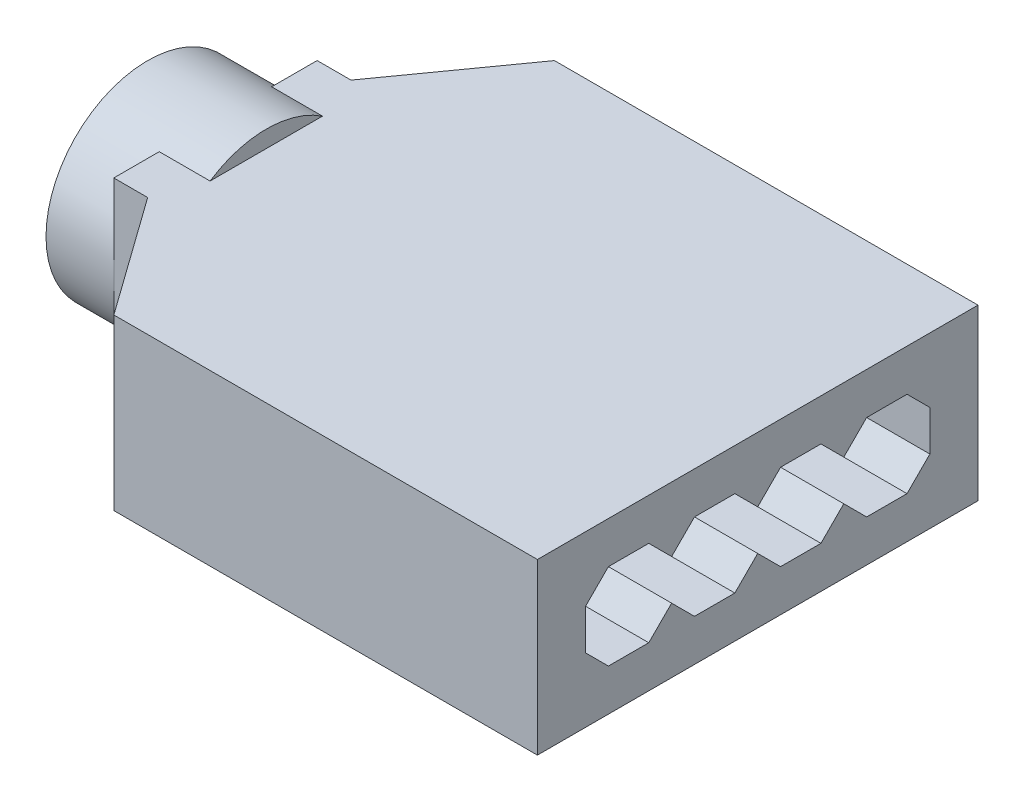
SolidWorks part; units mm, degrees
ref_plane "Alzado" through (0, 0, 0) normal (0, 0, 1) x (1, 0, 0)
ref_plane "Planta" through (0, 0, 0) normal (0, 1, 0) x (1, 0, 0)
ref_plane "Vista lateral" through (0, 0, 0) normal (1, 0, 0) x (0, 0, -1)
sketch "Croquis1" plane through (0, 0, 0) normal (1, 0, 0) x (0, 0, -1)
  line L0 (-0.5955, 1.27) -> (-1.27, 0.5955)
  line L1 (0.5955, 1.27) -> (-0.5955, 1.27)
  line L2 (1.27, 0.5955) -> (1.27, -0.5955)
  line L3 (0.5955, -1.27) -> (-0.5955, -1.27)
  line L4 (-1.27, 0.5955) -> (-1.27, -0.5955)
  line L5 (1.27, 1.27) -> (-1.27, -1.27) construction
  line L6 (1.27, -1.27) -> (-1.27, 1.27) construction
  line L7 (-0.5955, -1.27) -> (-1.27, -0.5955)
  line L8 (1.27, -0.5955) -> (0.5955, -1.27)
  line L9 (1.27, 0.5955) -> (0.5955, 1.27)
  line L10 (0, 0) -> (2.54, 0) construction
  line L11 (2.54, 0) -> (2.54, 3.1915) construction
  line L12 (0, 0) -> (0, 2.4434) construction
  line L13 (1.27, 0.5955) -> (1.27, 2.4434) construction
  line L14 (1.27, -0.5955) -> (1.9445, -1.27)
  line L15 (1.27, 0.5955) -> (1.9445, 1.27)
  line L16 (3.1355, -1.27) -> (3.81, -0.5955)
  line L17 (3.81, 0.5955) -> (3.81, -0.5955)
  line L18 (1.9445, -1.27) -> (3.1355, -1.27)
  line L19 (1.9445, 1.27) -> (3.1355, 1.27)
  line L20 (3.1355, 1.27) -> (3.81, 0.5955)
  line L21 (2.22, -0.32) -> (2.86, 0.32) construction
  line L22 (0.32, 0.32) -> (-0.32, 0.32)
  line L23 (0.32, 0.32) -> (0.32, -0.32)
  line L24 (0.32, -0.32) -> (-0.32, -0.32)
  line L25 (-0.32, 0.32) -> (-0.32, -0.32)
  line L26 (0.32, 0.32) -> (-0.32, -0.32) construction
  line L27 (0.32, -0.32) -> (-0.32, 0.32) construction
  line L28 (2.22, 0.32) -> (2.86, -0.32) construction
  line L29 (2.86, 0.32) -> (2.86, -0.32)
  line L30 (2.22, -0.32) -> (2.86, -0.32)
  line L31 (2.22, 0.32) -> (2.22, -0.32)
  line L32 (2.22, 0.32) -> (2.86, 0.32)
  line L34 (-6.77, 1.5) -> (4.23, 1.5)
  line L35 (-6.77, 1.5) -> (-6.77, -1.5)
  line L36 (-6.77, -1.5) -> (4.23, -1.5)
  line L37 (4.23, 1.5) -> (4.23, -1.5)
  line L38 (-6.77, 1.5) -> (4.23, -1.5) construction
  line L39 (-6.77, -1.5) -> (4.23, 1.5) construction
  point P0 (0, 0)
  point P33 (-1.27, 0)
  point P38 (0, 0)
  dimension "D1" = 2.54
  dimension "D2" = 2.54
  dimension "D3" = 2.54
  dimension "D4" = 0.64
  dimension "D5" = 0.64
  dimension "D6" = 3
  dimension "D7" = 11
extrude "Saliente-Extruir1" add sketch "Croquis1" along normal blind 2.54 contours L2 L9 L1 L0 L4 L7 L3 L8 L25 L22 L23 L24 | L20 L19 L15 L2 L14 L18 L16 L17 L31 L32 L29 L30 region at (0, 1.2341, 0) region at (0, 0.9073, -1.6327)
sketch "Croquis3" plane through (0, 0, 0) normal (1, 0, 0) x (0, 0, -1)
  line L1 (-0.32, -0.32) -> (0.32, -0.32)
  line L2 (-0.32, -0.32) -> (-0.32, 0.32)
  line L3 (-0.32, 0.32) -> (0.32, 0.32)
  line L4 (0.32, -0.32) -> (0.32, 0.32)
  line L5 (2.22, -0.32) -> (2.86, -0.32)
  line L6 (2.22, -0.32) -> (2.22, 0.32)
  line L7 (2.22, 0.32) -> (2.86, 0.32)
  line L8 (2.86, -0.32) -> (2.86, 0.32)
extrude "Saliente-Extruir2" add sketch "Croquis3" along normal blind 8.54 and the other way blind 3 separate body
chamfer "Chaflán1" distance 0.2 angle 45 8 edges at (-3, -0.32, 0) (-3, 0, -0.32) (-3, 0.32, 0) (-3, 0, 0.32) (8.54, 0.32, 0) (8.54, 0, -0.32) (8.54, -0.32, 0) (8.54, 0, 0.32)
chamfer "Chaflán2" distance 0.2 angle 45 8 edges at (8.54, 0.32, -2.54) (8.54, 0, -2.86) (8.54, -0.32, -2.54) (8.54, 0, -2.22) (-3, -0.32, -2.54) (-3, 0, -2.86) (-3, 0.32, -2.54) (-3, 0, -2.22)
mirror "Mirror3" about plane through (2.54, 0, 1.27) normal (0, 0, -1) of bodies 104 103
mirror "Mirror5" about plane through (2.54, 0, 1.27) normal (0, 0, -1) of bodies 101 102
extrude "Boss-Extrude6" add sketch "Croquis1<4>" along normal up to surface (2.54 mm away) separate body contours L37 L34 L35 L36 L19 L20 L17 L16 L18 L14 L8 L3 L7 L4 L0 L1 L9 L15 region at (0, 0, 2.5545) up to face at (2.54, 0, 0)
sketch "Croquis1<4>" plane through (0, 0, 0) normal (1, 0, 0) x (0, 0, -1) same geometry as "Croquis1"
combine bodies "Combine5" operation type subtract main body 121 bodies to subtract 104 103 107 108 110
sketch "Sketch6" plane through (0, 0, 0) normal (-1, 0, 0) x (0, 0, 1)
  line L1 (-4.23, 1.5) -> (6.77, 1.5)
  line L2 (-4.23, 1.5) -> (-4.23, -1.5)
  line L3 (-4.23, -1.5) -> (6.77, -1.5)
  line L4 (6.77, 1.5) -> (6.77, -1.5)
  circle A0 centre (-2.54, 0) radius 1
  circle A1 centre (0, 0.0136) radius 1
  circle A2 centre (2.54, 0) radius 1
  circle A3 centre (5.08, 0) radius 1
extrude "Boss-Extrude11" add sketch "Sketch6" along normal blind 0.8
sketch "Sketch7" plane through (2.54, 0, 0) normal (1, 0, 0) x (0, 0, -1)
  line L1 (-6.77, 1.5) -> (4.23, 1.5)
  line L2 (-6.77, 1.5) -> (-6.77, -1.5)
  line L3 (-6.77, -1.5) -> (4.23, -1.5)
  line L4 (4.23, 1.5) -> (4.23, -1.5)
  line L6 (-6.77, 1.5) -> (4.23, -1.5) construction
  line L7 (5.23, 2.5) -> (-7.77, 2.5)
  line L8 (5.23, 2.5) -> (5.23, -2.5)
  line L9 (5.23, -2.5) -> (-7.77, -2.5)
  line L10 (-7.77, 2.5) -> (-7.77, -2.5)
  line L11 (5.23, 2.5) -> (-7.77, -2.5) construction
  line L12 (5.23, -2.5) -> (-7.77, 2.5) construction
  line L13 (-6.77, -1.5) -> (4.23, 1.5) construction
  point P0 (-1.27, 0)
  point P13 (-1.27, 0)
extrude "Boss-Extrude12" add sketch "Sketch7" against normal blind 15
sketch "Sketch8" plane through (-12.46, 0, 0) normal (-1, 0, 0) x (0, 0, 1)
  line L1 (-5.23, 2.5) -> (7.77, 2.5)
  line L2 (-5.23, 2.5) -> (-5.23, -2.5)
  line L3 (-5.23, -2.5) -> (7.77, -2.5)
  line L4 (7.77, 2.5) -> (7.77, -2.5)
  circle A0 centre (1.27, 0) radius 2
extrude "Boss-Extrude13" add sketch "Sketch8" along normal blind 1
sketch "Sketch9" plane through (-13.46, 0, 0) normal (-1, 0, 0) x (0, 0, 1)
  circle A0 centre (1.27, 0) radius 2
  circle A1 centre (1.27, 0) radius 3
extrude "Boss-Extrude15" add sketch "Sketch9" against normal blind 1.5 and the other way blind 2
sketch "Sketch10" plane through (0, -1.5, 0) normal (0, 1, 0) x (1, 0, 0)
  line L1 (-12.46, 1.3281) -> (-12.46, 1.73) construction
  line L2 (-12.46, 1.3281) -> (-12.46, 4.23) construction
  line L8 (-0.8, 1) -> (-0.8, -1) construction
  line L9 (-12.46, -4.27) -> (-12.46, 1.73)
  line L13 (-11.96, -4.27) -> (-10.7899, -4.27)
  line L14 (-12.46, -4.27) -> (-11.96, -4.27)
  line L15 (-0.8, 4.23) -> (-0.8, -6.77) construction
  line L17 (-10.7899, 1.73) -> (-10.7899, -4.27)
  line L18 (-0.8, 1) -> (-0.8, 1.5056)
  line L19 (-0.8, -1.5056) -> (-0.8, -1)
  line L20 (-12.46, 1.73) -> (-10.7899, 1.73)
  line L23 (-0.8, 1.5056) -> (-4.8, 1.5056)
  line L24 (-4.8, 1.5056) -> (-4.8, 1)
  line L25 (-4.8, 1) -> (-0.8, 1)
  line L26 (-0.8, -1) -> (-4.8, -1)
  line L27 (-4.8, -1.5056) -> (-0.8, -1.5056)
  line L28 (-4.8, -1) -> (-4.8, -1.5056)
  line L30 (-0.8, -3.54) -> (-4.8, -3.54)
  line L32 (-4.8, -4.0456) -> (-0.8, -4.0456)
  line L33 (-4.8, -3.54) -> (-4.8, -4.0456)
  line M15 (-11.96, -3.8681) -> (-12.46, -3.8681)
  line M16 (-12.46, -3.8681) -> (-12.46, -6.77)
  line M20 (-12.46, 4.23) -> (-12.46, 1.3281)
  line M21 (-12.46, 1.3281) -> (-11.96, 1.3281)
  line M22 (-11.96, 1.3281) -> (-11.96, 0.0529)
  line M23 (-11.96, 0.0529) -> (-12.46, 0.0529)
  line M24 (-12.46, 0.0529) -> (-12.46, -2.5929)
  line M25 (-12.46, -2.5929) -> (-11.96, -2.5929)
  line M26 (-11.96, -2.5929) -> (-11.96, -3.8681)
extrude "Cut-Extrude2" cut sketch "Sketch10" along normal blind 3 contours L20 L14 L13 L17 M20 M21 M22 M23 M24 M25 M26 M15 M16 | L9 M15 M26 M25 | L9 M23 M22 M21 region at (-11.5396, -1.5, 1.27) region at (-12.21, -1.5, 3.2305) region at (-12.21, -1.5, -0.6905)
sketch "Sketch15" plane through (-12.46, 0, 0) normal (1, 0, 0) x (0, 0, -1)
  line L0 (4.23, -1.5) -> (4.23, 1.5)
  line L1 (4.23, 1.5) -> (0.0529, 1.5)
  line L3 (0.0529, -1.5) -> (4.23, -1.5)
  line L5 (-2.5929, -1.5) -> (-6.77, -1.5)
  line L6 (-6.77, 1.5) -> (-2.5929, 1.5)
  line L7 (-6.77, -1.5) -> (-6.77, 1.5)
  arc A0 (0.0529, -1.5) -> (0.0529, 1.5) centre (-1.27, 0) ccw
  arc A1 (-2.5929, -1.5) -> (-2.5929, 1.5) centre (-1.27, 0) cw
extrude "Boss-Extrude20" add sketch "Sketch15" along normal blind 3
sketch "Sketch16" plane through (0, 1.5, 0) normal (0, 1, 0) x (1, 0, 0)
  line L0 (-12.46, -2.5929) -> (-9.46, -6.77)
  line L1 (-9.46, -6.77) -> (-9.46, -2.5929)
  line L2 (-9.46, -2.5929) -> (-12.46, -2.5929) construction
  line L3 (-9.46, -2.5929) -> (-9.46, -6.77) construction
  line L4 (-9.46, -2.5929) -> (-12.46, -2.5929)
  line L5 (-12.46, -2.5929) -> (-12.46, -6.77)
  line L6 (-12.46, -6.77) -> (-9.46, -6.77)
  line L9 (-12.46, 4.23) -> (-9.46, 4.23)
  line L10 (-12.46, 0.0529) -> (-12.46, 4.23)
  line L11 (-9.46, 0.0529) -> (-12.46, 0.0529)
  line L12 (-9.46, 4.23) -> (-9.46, 0.0529)
  line L13 (-12.46, 0.0529) -> (-9.46, 4.23)
extrude "Cut-Extrude3" cut sketch "Sketch16" against normal blind 3 contours L0 | L13 L11 L12 region at (-10.46, 1.5, 3.9853) region at (-10.46, 1.5, -1.4453)
sketch3d "3DSketch1"
  point P0 (-11.7541, 1.5, -3.0659)
ref_plane "Plane2" through (0, 1.5, 0) normal (0, 1, 0) x (1, 0, 0)
sketch "Sketch19" plane through (0, 1.5, 0) normal (0, 1, 0) x (1, 0, 0)
  line L8 (-12.46, -1.27) -> (-14.4452, -1.27) construction
  line L9 (-13.46, 5.23) -> (2.54, 5.23) construction
  line L14 (-12.46, 0.0529) -> (-9.46, 4.23)
  line L16 (-13.46, 1.73) -> (-15.46, 1.73) construction
  line L17 (-13.46, 1.73) -> (-13.46, 0.3883) construction
  line L18 (-13.46, 1.73) -> (-12.46, 1.73)
  line L19 (-9.46, 4.23) -> (-8.7418, 5.23)
  line L20 (-12.46, 1.73) -> (-10.1671, 4.9371)
  line L21 (-10.1671, 4.9371) -> (-9.9577, 5.23)
  line L22 (-13.46, 1.73) -> (-13.46, 5.23)
  line L23 (-13.46, 5.23) -> (-9.9577, 5.23)
  line L24 (-12.46, -2.5929) -> (-12.46, 0.0529) construction
  line L25 (-13.46, -7.77) -> (-9.9577, -7.77)
  line L26 (-13.46, -4.27) -> (-13.46, -7.77)
  line L27 (-10.1671, -7.4771) -> (-9.9577, -7.77)
  line L28 (-12.46, -4.27) -> (-10.1671, -7.4771)
  line L29 (-13.46, -4.27) -> (-12.46, -4.27)
extrude "Cut-Extrude5" cut sketch "Sketch19" against normal through all and the other way through all contours L23 L22 L18 L20 L21 | L29 L26 L25 L27 L28 region at (-12.2185, 1.5, -3.8042) region at (-12.2185, 1.5, 6.3442)
